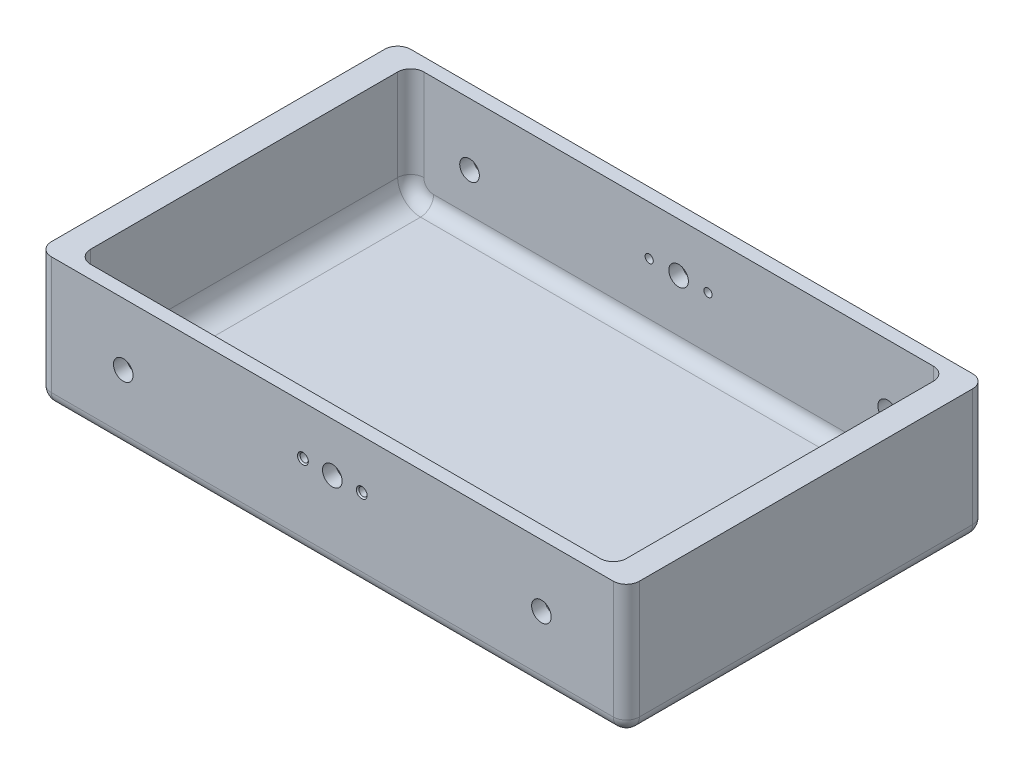
SolidWorks part; units mm, degrees
ref_plane "Front Plane" through (0, 0, 0) normal (0, 0, 1) x (1, 0, 0)
ref_plane "Top Plane" through (0, 0, 0) normal (0, 1, 0) x (1, 0, 0)
ref_plane "Right Plane" through (0, 0, 0) normal (1, 0, 0) x (0, 0, -1)
sketch "Esquisse1" plane through (0, 0, 0) normal (0, 0, 1) x (1, 0, 0)
  line L0 (0, 0) -> (0, 20) construction
  line L9 (-45, 20) -> (45, 20)
  line L10 (-45, 20) -> (-45, 0)
  line L11 (-45, 0) -> (45, 0)
  line L12 (45, 20) -> (45, 0)
  circle A0 centre (-32, 10.5) radius 1.5
  circle A1 centre (32, 10.5) radius 1.5
  circle A2 centre (0, 12.5) radius 1.5
  point P5 (0, 0)
  dimension "D3" = 3
  dimension "D8" = 3
  dimension "D1" = 20
  dimension "D2" = 90
  dimension "D4" = 32
  dimension "D5" = 9.5
  dimension "D6" = 9.5
  dimension "D7" = 32
  dimension "D9" = 7.5
extrude "Boss.-Extru.1" add sketch "Esquisse1" along normal blind 2
sketch "Esquisse2" plane through (0, 0, 2) normal (0, 0, 1) x (1, 0, 0)
  line L1 (-45, 20) -> (45, 20)
  line L2 (-45, 20) -> (-45, 0)
  line L3 (-45, 0) -> (45, 0)
  line L4 (45, 20) -> (45, 0)
  dimension "D1" = 20
extrude "Boss.-Extru.2" add sketch "Esquisse2" along normal blind 51
sketch "Esquisse4" plane through (0, 0, 53) normal (0, 0, 1) x (1, 0, 0)
  line L0 (0, 0) -> (0, 16.2488) construction
  line L1 (-37.5, 6) -> (37.5, 6) construction
  line L3 (-37.5, 2.5) -> (37.5, 2.5)
  line L4 (-41, 6) -> (-41, 20)
  line L5 (45, 20) -> (-45, 20) construction
  line L6 (41, 6) -> (41, 20)
  line L7 (41, 20) -> (-41, 20)
  arc A0 (-41, 6) -> (-37.5, 2.5) centre (-37.5, 6) ccw
  arc A1 (37.5, 2.5) -> (41, 6) centre (37.5, 6) ccw
  point P5 (0, 6.6299)
  dimension "D2" = 3.5
  dimension "D1" = 75
  dimension "D3" = 14
extrude "Enlèv. mat.-Extru.2" cut sketch "Esquisse4" against normal blind 51
sketch "Esquisse6" plane through (0, 0, 53) normal (0, 0, 1) x (1, 0, 0)
  line L4 (-45, 20) -> (-45, 0)
  line L5 (45, 20) -> (-45, 20)
  line L6 (45, 0) -> (45, 20)
  line L7 (-45, 0) -> (45, 0)
  line L8 (-45, 20) -> (-45, 0)
  line L9 (45, 20) -> (-45, 20)
  line L10 (45, 0) -> (45, 20)
  line L11 (-45, 0) -> (45, 0)
  circle A0 centre (32, 10.5) radius 1.5 construction
  circle A1 centre (0, 12.5) radius 1.5 construction
  circle A2 centre (-32, 10.5) radius 1.5 construction
  circle A3 centre (32, 10.5) radius 1.5
  circle A4 centre (0, 12.5) radius 1.5
  circle A5 centre (-32, 10.5) radius 1.5
  dimension "D1" = 0
extrude "Boss.-Extru.4" add sketch "Esquisse6" along normal blind 2
hole_wizard "Trou taraudé M1.61" positions "Esquisse7" profile "Esquisse8" tap size "M1.6" standard "ISO" end condition up to next
sketch "Esquisse7" plane through (0, 0, 55) normal (0, 0, 1) x (1, 0, 0)
  line L0 (0, 0) -> (0, 13.003) construction
  line L3 (-2.0559, 12.5) -> (2.2659, 12.5) construction
  circle A0 centre (0, 12.5) radius 1.5 construction
  circle A1 centre (0, 12.5) radius 1.5
  point P0 (-4.5, 12.5)
  point P2 (4.5, 12.5)
  dimension "D1" = 4.5
  dimension "D2" = 4.5
sketch "Esquisse8" plane through (-4.5, 12.5, 55) normal (1, 0, 0) x (0, -1, 0)
  line L0 (0, 0) -> (0, 2)
  line L1 (0, 2) -> (0.625, 2)
  line L2 (0.625, 2) -> (0.625, 0.2)
  line L3 (0.625, 0.2) -> (0.825, 0)
  line L5 (0.825, 0) -> (0, 0)
  line L6 (-0.625, 0.2) -> (-0.825, 0) construction
  line L11 (0, -6.35) -> (0, 107.95) construction
  dimension "Diamètre du trou pour taraudage jusqu'au prochain" = 1.25
  dimension "Profondeur du trou pour taraudage jusqu'au prochain" = 2
  dimension "Diamètre du fraisage entrant" = 1.65
  dimension "Angle du fraisage entrant" = 90
cosmetic thread "Filetage de perçage1" parameters "D2"=1.6
cosmetic thread "Filetage de perçage2" parameters "D2"=1.6
hole_wizard "Trou taraudé M1.62" positions "Esquisse9" profile "Esquisse10" tap size "M1.6" standard "ISO" end condition up to next
sketch "Esquisse9" plane through (0, 0, 0) normal (0, 0, -1) x (-1, 0, 0)
  line L0 (0, 0) -> (0, 12.497) construction
  line L2 (-3.3521, 12.497) -> (3.0838, 12.497) construction
  point P0 (-4.5, 12.497)
  point P2 (4.5, 12.497)
  dimension "D1" = 4.5
  dimension "D2" = 4.5
sketch "Esquisse10" plane through (4.5, 12.497, 0) normal (1, 0, 0) x (0, 1, 0)
  line L0 (0, 0) -> (0, 2)
  line L1 (0, 2) -> (0.625, 2)
  line L2 (0.625, 2) -> (0.625, 0.2)
  line L3 (0.625, 0.2) -> (0.825, 0)
  line L5 (0.825, 0) -> (0, 0)
  line L6 (-0.625, 0.2) -> (-0.825, 0) construction
  line L11 (0, -6.35) -> (0, 107.95) construction
  dimension "Diamètre du trou pour taraudage jusqu'au prochain" = 1.25
  dimension "Profondeur du trou pour taraudage jusqu'au prochain" = 2
  dimension "Diamètre du fraisage entrant" = 1.65
  dimension "Angle du fraisage entrant" = 90
cosmetic thread "Filetage de perçage3" parameters "D2"=1.6
cosmetic thread "Filetage de perçage4" parameters "D2"=1.6
fillet "Congé1" radius 2 5 edges at (-41, 13, 2) (-39.9749, 3.5251, 2) (41, 13, 2) (39.9749, 3.5251, 2) (0, 2.5, 2)
fillet "Congé2" radius 2 5 edges at (-41, 13, 53) (-39.9749, 3.5251, 53) (41, 13, 53) (39.9749, 3.5251, 53) (0, 2.5, 53)
fillet "Congé3" radius 2 4 edges at (-45, 0, 27.5) (0, 0, 55) (0, 0, 0) (45, 0, 27.5)
fillet "Congé4" radius 2 8 edges at (44.4142, 0.5858, 54.4142) (-44.4142, 0.5858, 54.4142) (-44.4142, 0.5858, 0.5858) (44.4142, 0.5858, 0.5858) (45, 11, 55) (-45, 11, 55) (-45, 11, 0) (45, 11, 0)
